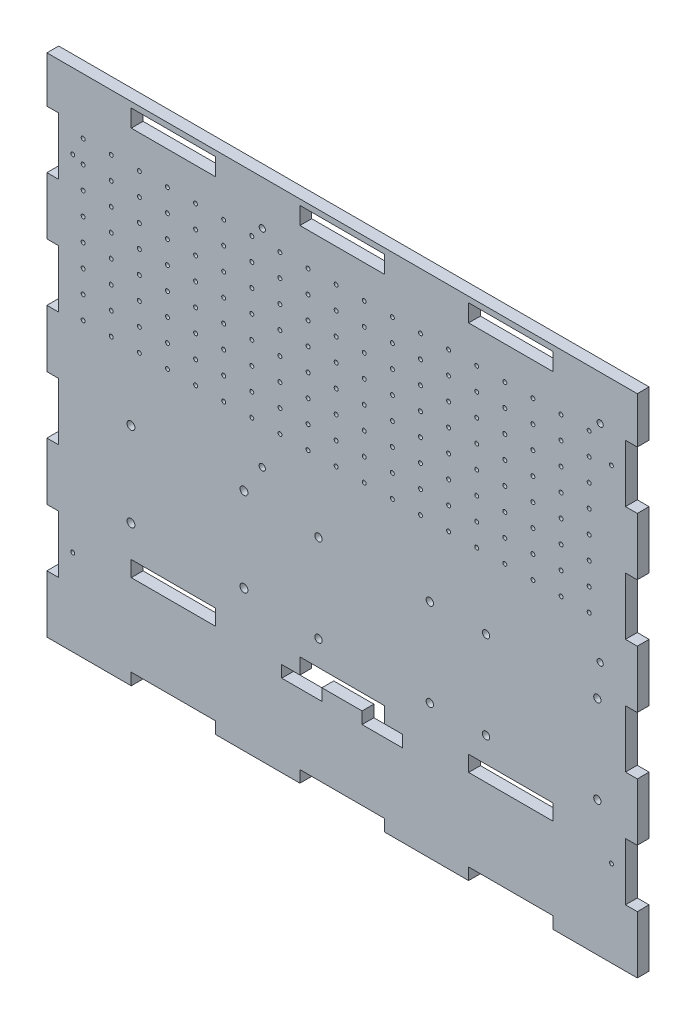
SolidWorks part; units mm, degrees
ref_plane "Front Plane" through (0, 0, 0) normal (0, 0, 1) x (1, 0, 0)
ref_plane "Top Plane" through (0, 0, 0) normal (0, 1, 0) x (1, 0, 0)
ref_plane "Right Plane" through (0, 0, 0) normal (1, 0, 0) x (0, 0, -1)
sketch "Sketch1" plane through (0, 0, 0) normal (0, 0, 1) x (1, 0, 0)
  line L1 (-127.8759, 139.2641) -> (138.8241, 139.2641)
  line L2 (-127.8759, 139.2641) -> (-127.8759, -84.2559)
  line L3 (-127.8759, -84.2559) -> (138.8241, -84.2559)
  line L4 (138.8241, 139.2641) -> (138.8241, -84.2559)
  dimension "D1" = 266.7
  dimension "D2" = 223.52
extrude "Boss-Extrude1" add sketch "Sketch1" along normal blind 5.334
sketch "Sketch2" plane through (0, 0, 5.334) normal (0, 0, 1) x (1, 0, 0)
  line L0 (-127.8759, -84.2559) -> (138.8241, -84.2559) construction
  line L1 (-89.7759, -84.2559) -> (-51.6759, -84.2559)
  line L2 (-89.7759, -84.2559) -> (-89.7759, -78.9219)
  line L3 (-89.7759, -78.9219) -> (-51.6759, -78.9219)
  line L4 (-51.6759, -84.2559) -> (-51.6759, -78.9219)
  line L5 (-89.7759, -78.9219) -> (-127.8759, -78.9219) construction
  line L6 (-13.5759, -84.2559) -> (24.5241, -84.2559)
  line L7 (-13.5759, -84.2559) -> (-13.5759, -78.9219)
  line L8 (-13.5759, -78.9219) -> (24.5241, -78.9219)
  line L9 (24.5241, -84.2559) -> (24.5241, -78.9219)
  line L10 (62.6241, -84.2559) -> (100.7241, -84.2559)
  line L11 (62.6241, -84.2559) -> (62.6241, -78.9219)
  line L12 (62.6241, -78.9219) -> (100.7241, -78.9219)
  line L13 (100.7241, -84.2559) -> (100.7241, -78.9219)
  line L14 (-127.8759, 139.2641) -> (-127.8759, -84.2559) construction
  line L15 (-51.6759, -78.9219) -> (-13.5759, -78.9219) construction
  line L16 (24.5241, -78.9219) -> (62.6241, -78.9219) construction
  line L17 (62.6241, -78.9219) -> (62.364, -79.7896) construction
  line L18 (100.7241, -78.9219) -> (138.8241, -78.9219) construction
  line L19 (138.8241, -84.2559) -> (138.8241, 139.2641) construction
  line L20 (-127.8759, 27.5041) -> (138.8241, 27.5041) construction
  line L21 (100.7241, 139.2641) -> (100.7241, 133.9301)
  line L22 (62.6241, 133.9301) -> (100.7241, 133.9301)
  line L23 (62.6241, 139.2641) -> (62.6241, 133.9301)
  line L24 (24.5241, 139.2641) -> (24.5241, 133.9301)
  line L25 (-13.5759, 133.9301) -> (24.5241, 133.9301)
  line L26 (-13.5759, 139.2641) -> (-13.5759, 133.9301)
  line L27 (-51.6759, 139.2641) -> (-51.6759, 133.9301)
  line L28 (-89.7759, 133.9301) -> (-51.6759, 133.9301)
  line L29 (-89.7759, 139.2641) -> (-89.7759, 133.9301)
  line L30 (62.6241, 139.2641) -> (100.7241, 139.2641)
  line L31 (-13.5759, 139.2641) -> (24.5241, 139.2641)
  line L32 (-89.7759, 139.2641) -> (-51.6759, 139.2641)
  dimension "D1" = 5.334
extrude "Cut-Extrude1" cut sketch "Sketch2" against normal through all
sketch "Sketch5" plane through (0, 0, 5.334) normal (0, 0, 1) x (1, 0, 0)
  line L0 (-51.6759, -34.8224) -> (-13.5759, -34.8224) construction
  line L1 (-89.7759, -34.8224) -> (-51.6759, -34.8224)
  line L2 (-89.7759, -34.8224) -> (-89.7759, -41.9344)
  line L3 (-89.7759, -41.9344) -> (-51.6759, -41.9344)
  line L4 (-51.6759, -34.8224) -> (-51.6759, -41.9344)
  line L5 (-13.5759, -34.8224) -> (24.5241, -34.8224)
  line L6 (-13.5759, -34.8224) -> (-13.5759, -41.9344)
  line L7 (-13.5759, -41.9344) -> (24.5241, -41.9344)
  line L8 (24.5241, -34.8224) -> (24.5241, -41.9344)
  line L9 (62.6241, -34.8224) -> (100.7241, -34.8224)
  line L10 (62.6241, -34.8224) -> (62.6241, -41.9344)
  line L11 (62.6241, -41.9344) -> (100.7241, -41.9344)
  line L12 (100.7241, -34.8224) -> (100.7241, -41.9344)
  line L13 (-51.6759, -41.9344) -> (-13.5759, -41.9344) construction
  line L14 (24.5241, -34.8224) -> (62.6241, -34.8224) construction
  line L15 (24.5241, -41.9344) -> (62.6241, -41.9344) construction
  line L16 (-89.7759, -34.8224) -> (-127.8759, -34.8224) construction
  line L17 (-127.8759, 139.2641) -> (-127.8759, -84.2559) construction
  line L18 (-89.7759, -41.9344) -> (-127.8759, -41.9344) construction
  line L19 (100.7241, -34.8224) -> (138.8241, -34.8224) construction
  line L20 (138.8241, -84.2559) -> (138.8241, 139.2641) construction
  line L21 (100.7241, -41.9344) -> (138.8241, -41.9344) construction
  dimension "D1" = 7.112
extrude "Cut-Extrude3" cut sketch "Sketch5" against normal through all
sketch "Sketch8" plane through (0, 0, 5.334) normal (0, 0, 1) x (1, 0, 0)
  line L0 (-13.5759, -41.9344) -> (24.5241, -41.9344) construction
  line L1 (-21.7977, -47.2684) -> (-3.6478, -47.2684)
  line L2 (-21.7977, -47.2684) -> (-21.7977, -41.9344)
  line L3 (-21.7977, -41.9344) -> (-3.6478, -41.9344)
  line L4 (-3.6478, -47.2684) -> (-3.6478, -41.9344)
  line L5 (-3.6478, -47.2684) -> (14.5022, -47.2684) construction
  line L6 (14.5022, -41.9344) -> (32.6521, -41.9344)
  line L7 (14.5022, -41.9344) -> (14.5022, -47.2684)
  line L8 (14.5022, -47.2684) -> (32.6521, -47.2684)
  line L9 (32.6521, -41.9344) -> (32.6521, -47.2684)
  line L10 (14.5022, -47.2684) -> (14.3218, -49.4005) construction
  line L11 (14.5022, -41.9344) -> (-3.6478, -41.9344) construction
  line L12 (62.6241, -34.8224) -> (62.6241, -41.9344) construction
  line L13 (-51.6759, -41.9344) -> (-51.6759, -34.8224) construction
  dimension "D1" = 5.334
  dimension "D2" = 29.972
  dimension "D3" = 29.8782
extrude "Cut-Extrude6" cut sketch "Sketch8" against normal through all
sketch "Sketch9" plane through (0, 0, 5.334) normal (0, 0, 1) x (1, 0, 0)
  line L0 (-111.5143, 118.9789) -> (-98.8143, 118.9789) construction
  line L1 (-111.5143, 108.8189) -> (-98.8143, 108.8189) construction
  line L2 (-111.5143, 98.6589) -> (-98.8143, 98.6589) construction
  line L3 (-111.5143, 88.4989) -> (-98.8143, 88.4989) construction
  line L4 (-111.5143, 78.3389) -> (-98.8143, 78.3389) construction
  line L5 (-111.5143, 68.1789) -> (-98.8143, 68.1789) construction
  line L6 (-111.5143, 58.0189) -> (-98.8143, 58.0189) construction
  line L7 (-111.5143, 47.8589) -> (-98.8143, 47.8589) construction
  line L8 (-111.5143, 118.9789) -> (-111.5143, 108.8189) construction
  circle A0 centre (-111.5143, 118.9789) radius 0.889
  circle A1 centre (-98.8143, 118.9789) radius 0.889
  circle A2 centre (-86.1143, 118.9789) radius 0.889
  circle A3 centre (-73.4143, 118.9789) radius 0.889
  circle A4 centre (-60.7143, 118.9789) radius 0.889
  circle A5 centre (-48.0143, 118.9789) radius 0.889
  circle A6 centre (-35.3143, 118.9789) radius 0.889
  circle A7 centre (-22.6143, 118.9789) radius 0.889
  circle A8 centre (-9.9143, 118.9789) radius 0.889
  circle A9 centre (2.7857, 118.9789) radius 0.889
  circle A10 centre (15.4857, 118.9789) radius 0.889
  circle A11 centre (28.1857, 118.9789) radius 0.889
  circle A12 centre (40.8857, 118.9789) radius 0.889
  circle A13 centre (53.5857, 118.9789) radius 0.889
  circle A14 centre (66.2857, 118.9789) radius 0.889
  circle A15 centre (78.9857, 118.9789) radius 0.889
  circle A16 centre (91.6857, 118.9789) radius 0.889
  circle A17 centre (104.3857, 118.9789) radius 0.889
  circle A18 centre (117.0857, 118.9789) radius 0.889
  circle A19 centre (-111.5143, 108.8189) radius 0.889
  circle A20 centre (-98.8143, 108.8189) radius 0.889
  circle A21 centre (-86.1143, 108.8189) radius 0.889
  circle A22 centre (-73.4143, 108.8189) radius 0.889
  circle A23 centre (-60.7143, 108.8189) radius 0.889
  circle A24 centre (-48.0143, 108.8189) radius 0.889
  circle A25 centre (-35.3143, 108.8189) radius 0.889
  circle A26 centre (-22.6143, 108.8189) radius 0.889
  circle A27 centre (-9.9143, 108.8189) radius 0.889
  circle A28 centre (2.7857, 108.8189) radius 0.889
  circle A29 centre (15.4857, 108.8189) radius 0.889
  circle A30 centre (28.1857, 108.8189) radius 0.889
  circle A31 centre (40.8857, 108.8189) radius 0.889
  circle A32 centre (53.5857, 108.8189) radius 0.889
  circle A33 centre (66.2857, 108.8189) radius 0.889
  circle A34 centre (78.9857, 108.8189) radius 0.889
  circle A35 centre (91.6857, 108.8189) radius 0.889
  circle A36 centre (104.3857, 108.8189) radius 0.889
  circle A37 centre (117.0857, 108.8189) radius 0.889
  circle A38 centre (-111.5143, 98.6589) radius 0.889
  circle A39 centre (-98.8143, 98.6589) radius 0.889
  circle A40 centre (-86.1143, 98.6589) radius 0.889
  circle A41 centre (-73.4143, 98.6589) radius 0.889
  circle A42 centre (-60.7143, 98.6589) radius 0.889
  circle A43 centre (-48.0143, 98.6589) radius 0.889
  circle A44 centre (-35.3143, 98.6589) radius 0.889
  circle A45 centre (-22.6143, 98.6589) radius 0.889
  circle A46 centre (-9.9143, 98.6589) radius 0.889
  circle A47 centre (2.7857, 98.6589) radius 0.889
  circle A48 centre (15.4857, 98.6589) radius 0.889
  circle A49 centre (28.1857, 98.6589) radius 0.889
  circle A50 centre (40.8857, 98.6589) radius 0.889
  circle A51 centre (53.5857, 98.6589) radius 0.889
  circle A52 centre (66.2857, 98.6589) radius 0.889
  circle A53 centre (78.9857, 98.6589) radius 0.889
  circle A54 centre (91.6857, 98.6589) radius 0.889
  circle A55 centre (104.3857, 98.6589) radius 0.889
  circle A56 centre (117.0857, 98.6589) radius 0.889
  circle A57 centre (-111.5143, 88.4989) radius 0.889
  circle A58 centre (-98.8143, 88.4989) radius 0.889
  circle A59 centre (-86.1143, 88.4989) radius 0.889
  circle A60 centre (-73.4143, 88.4989) radius 0.889
  circle A61 centre (-60.7143, 88.4989) radius 0.889
  circle A62 centre (-48.0143, 88.4989) radius 0.889
  circle A63 centre (-35.3143, 88.4989) radius 0.889
  circle A64 centre (-22.6143, 88.4989) radius 0.889
  circle A65 centre (-9.9143, 88.4989) radius 0.889
  circle A66 centre (2.7857, 88.4989) radius 0.889
  circle A67 centre (15.4857, 88.4989) radius 0.889
  circle A68 centre (28.1857, 88.4989) radius 0.889
  circle A69 centre (40.8857, 88.4989) radius 0.889
  circle A70 centre (53.5857, 88.4989) radius 0.889
  circle A71 centre (66.2857, 88.4989) radius 0.889
  circle A72 centre (78.9857, 88.4989) radius 0.889
  circle A73 centre (91.6857, 88.4989) radius 0.889
  circle A74 centre (104.3857, 88.4989) radius 0.889
  circle A75 centre (117.0857, 88.4989) radius 0.889
  circle A76 centre (-111.5143, 78.3389) radius 0.889
  circle A77 centre (-98.8143, 78.3389) radius 0.889
  circle A78 centre (-86.1143, 78.3389) radius 0.889
  circle A79 centre (-73.4143, 78.3389) radius 0.889
  circle A80 centre (-60.7143, 78.3389) radius 0.889
  circle A81 centre (-48.0143, 78.3389) radius 0.889
  circle A82 centre (-35.3143, 78.3389) radius 0.889
  circle A83 centre (-22.6143, 78.3389) radius 0.889
  circle A84 centre (-9.9143, 78.3389) radius 0.889
  circle A85 centre (2.7857, 78.3389) radius 0.889
  circle A86 centre (15.4857, 78.3389) radius 0.889
  circle A87 centre (28.1857, 78.3389) radius 0.889
  circle A88 centre (40.8857, 78.3389) radius 0.889
  circle A89 centre (53.5857, 78.3389) radius 0.889
  circle A90 centre (66.2857, 78.3389) radius 0.889
  circle A91 centre (78.9857, 78.3389) radius 0.889
  circle A92 centre (91.6857, 78.3389) radius 0.889
  circle A93 centre (104.3857, 78.3389) radius 0.889
  circle A94 centre (117.0857, 78.3389) radius 0.889
  circle A95 centre (-111.5143, 68.1789) radius 0.889
  circle A96 centre (-98.8143, 68.1789) radius 0.889
  circle A97 centre (-86.1143, 68.1789) radius 0.889
  circle A98 centre (-73.4143, 68.1789) radius 0.889
  circle A99 centre (-60.7143, 68.1789) radius 0.889
  circle A100 centre (-48.0143, 68.1789) radius 0.889
  circle A101 centre (-35.3143, 68.1789) radius 0.889
  circle A102 centre (-22.6143, 68.1789) radius 0.889
  circle A103 centre (-9.9143, 68.1789) radius 0.889
  circle A104 centre (2.7857, 68.1789) radius 0.889
  circle A105 centre (15.4857, 68.1789) radius 0.889
  circle A106 centre (28.1857, 68.1789) radius 0.889
  circle A107 centre (40.8857, 68.1789) radius 0.889
  circle A108 centre (53.5857, 68.1789) radius 0.889
  circle A109 centre (66.2857, 68.1789) radius 0.889
  circle A110 centre (78.9857, 68.1789) radius 0.889
  circle A111 centre (91.6857, 68.1789) radius 0.889
  circle A112 centre (104.3857, 68.1789) radius 0.889
  circle A113 centre (117.0857, 68.1789) radius 0.889
  circle A114 centre (-111.5143, 58.0189) radius 0.889
  circle A115 centre (-98.8143, 58.0189) radius 0.889
  circle A116 centre (-86.1143, 58.0189) radius 0.889
  circle A117 centre (-73.4143, 58.0189) radius 0.889
  circle A118 centre (-60.7143, 58.0189) radius 0.889
  circle A119 centre (-48.0143, 58.0189) radius 0.889
  circle A120 centre (-35.3143, 58.0189) radius 0.889
  circle A121 centre (-22.6143, 58.0189) radius 0.889
  circle A122 centre (-9.9143, 58.0189) radius 0.889
  circle A123 centre (2.7857, 58.0189) radius 0.889
  circle A124 centre (15.4857, 58.0189) radius 0.889
  circle A125 centre (28.1857, 58.0189) radius 0.889
  circle A126 centre (40.8857, 58.0189) radius 0.889
  circle A127 centre (53.5857, 58.0189) radius 0.889
  circle A128 centre (66.2857, 58.0189) radius 0.889
  circle A129 centre (78.9857, 58.0189) radius 0.889
  circle A130 centre (91.6857, 58.0189) radius 0.889
  circle A131 centre (104.3857, 58.0189) radius 0.889
  circle A132 centre (117.0857, 58.0189) radius 0.889
  circle A133 centre (-111.5143, 47.8589) radius 0.889
  circle A134 centre (-98.8143, 47.8589) radius 0.889
  circle A135 centre (-86.1143, 47.8589) radius 0.889
  circle A136 centre (-73.4143, 47.8589) radius 0.889
  circle A137 centre (-60.7143, 47.8589) radius 0.889
  circle A138 centre (-48.0143, 47.8589) radius 0.889
  circle A139 centre (-35.3143, 47.8589) radius 0.889
  circle A140 centre (-22.6143, 47.8589) radius 0.889
  circle A141 centre (-9.9143, 47.8589) radius 0.889
  circle A142 centre (2.7857, 47.8589) radius 0.889
  circle A143 centre (15.4857, 47.8589) radius 0.889
  circle A144 centre (28.1857, 47.8589) radius 0.889
  circle A145 centre (40.8857, 47.8589) radius 0.889
  circle A146 centre (53.5857, 47.8589) radius 0.889
  circle A147 centre (66.2857, 47.8589) radius 0.889
  circle A148 centre (78.9857, 47.8589) radius 0.889
  circle A149 centre (91.6857, 47.8589) radius 0.889
  circle A150 centre (104.3857, 47.8589) radius 0.889
  circle A151 centre (117.0857, 47.8589) radius 0.889
  dimension "D1" = 19
  dimension "D5" = 1.778
  dimension "D2" = 12.7
  dimension "D4" = 10.16
  dimension "D3" = 8
extrude "Cut-Extrude7" cut sketch "Sketch9" against normal through all
sketch "Sketch10" plane through (0, 139.2641, 0) normal (0, 1, 0) x (1, 0, 0)
  line L0 (-13.5759, -5.334) -> (-51.6759, -5.334) construction
  line L1 (-51.6759, 0) -> (-13.5759, 0)
  line L2 (-51.6759, 0) -> (-51.6759, -5.334)
  line L3 (-51.6759, -5.334) -> (-13.5759, -5.334)
  line L4 (-13.5759, 0) -> (-13.5759, -5.334)
extrude "Boss-Extrude2" add sketch "Sketch10" along normal blind 10.16
sketch "Sketch12" plane through (-51.6759, 0, 0) normal (-1, 0, 0) x (0, 0, 1)
  line L0 (0, 133.9301) -> (0, 149.4241) construction
  line L1 (5.334, 149.4241) -> (0, 149.4241)
  line L2 (5.334, 149.4241) -> (5.334, 141.8041)
  line L3 (5.334, 141.8041) -> (0, 141.8041)
  line L4 (0, 149.4241) -> (0, 141.8041)
  dimension "D1" = 7.62
extrude "Boss-Extrude3" add sketch "Sketch12" along normal blind 76.2 and the other way blind 190.5
sketch "Sketch13" plane through (0, 139.2641, 0) normal (0, 1, 0) x (1, 0, 0)
  line L1 (-127.8759, 0) -> (-89.7759, 0)
  line L2 (-127.8759, 0) -> (-127.8759, -5.334)
  line L3 (-127.8759, -5.334) -> (-89.7759, -5.334)
  line L4 (-89.7759, 0) -> (-89.7759, -5.334)
extrude "Boss-Extrude4" add sketch "Sketch13" along normal blind 2.54
sketch "Sketch14" plane through (0, 139.2641, 0) normal (0, 1, 0) x (1, 0, 0)
  line L1 (24.5241, 0) -> (62.6241, 0)
  line L2 (24.5241, 0) -> (24.5241, -5.334)
  line L3 (24.5241, -5.334) -> (62.6241, -5.334)
  line L4 (62.6241, 0) -> (62.6241, -5.334)
extrude "Boss-Extrude5" add sketch "Sketch14" along normal blind 2.54
sketch "Sketch15" plane through (0, 139.2641, 0) normal (0, 1, 0) x (1, 0, 0)
  line L1 (100.7241, 0) -> (138.8241, 0)
  line L2 (100.7241, 0) -> (100.7241, -5.334)
  line L3 (100.7241, -5.334) -> (138.8241, -5.334)
  line L4 (138.8241, 0) -> (138.8241, -5.334)
extrude "Boss-Extrude6" add sketch "Sketch15" along normal blind 2.54
sketch "Sketch16" plane through (0, 0, 5.334) normal (0, 0, 1) x (1, 0, 0)
  line L0 (-127.8759, 149.4241) -> (-127.8759, -84.2559) construction
  line L1 (-127.8759, -32.327) -> (-122.5419, -32.327)
  line L2 (-127.8759, -32.327) -> (-127.8759, -58.2914)
  line L3 (-127.8759, -58.2914) -> (-122.5419, -58.2914)
  line L4 (-122.5419, -32.327) -> (-122.5419, -58.2914)
  line L5 (-122.5419, -32.327) -> (-122.5419, -6.3625) construction
  line L6 (-127.8759, 19.6019) -> (-122.5419, 19.6019)
  line L7 (-122.5419, -58.2914) -> (-122.5419, -84.2559) construction
  line L8 (-127.8759, -84.2559) -> (-89.7759, -84.2559) construction
  line L9 (-127.8759, 19.6019) -> (-127.8759, -6.3625)
  line L10 (-127.8759, -6.3625) -> (-122.5419, -6.3625)
  line L11 (-122.5419, 19.6019) -> (-122.5419, -6.3625)
  line L12 (-122.5419, 19.6019) -> (-122.5419, 45.5664) construction
  line L13 (5.4741, -78.9219) -> (5.4741, 149.4241) construction
  line L14 (-127.8759, 71.5308) -> (-122.5419, 71.5308)
  line L15 (-127.8759, 71.5308) -> (-127.8759, 45.5664)
  line L16 (-127.8759, 45.5664) -> (-122.5419, 45.5664)
  line L17 (-122.5419, 71.5308) -> (-122.5419, 45.5664)
  line L18 (-122.5419, 71.5308) -> (-122.5419, 97.4953) construction
  line L19 (24.5241, -78.9219) -> (-13.5759, -78.9219) construction
  line L20 (-127.8759, 97.4953) -> (-122.5419, 97.4953)
  line L21 (-127.8759, 97.4953) -> (-127.8759, 123.4597)
  line L22 (-127.8759, 123.4597) -> (-122.5419, 123.4597)
  line L23 (-122.5419, 97.4953) -> (-122.5419, 123.4597)
  line L24 (-122.5419, 123.4597) -> (-122.5419, 149.4241) construction
  line L25 (-127.8759, 149.4241) -> (138.8241, 149.4241) construction
  line L26 (133.4901, 123.4597) -> (133.4901, 149.4241) construction
  line L27 (133.4901, 71.5308) -> (133.4901, 97.4953) construction
  line L28 (133.4901, 19.6019) -> (133.4901, 45.5664) construction
  line L29 (133.4901, -58.2914) -> (133.4901, -84.2559) construction
  line L30 (133.4901, -32.327) -> (133.4901, -6.3625) construction
  line L31 (133.4901, 97.4953) -> (133.4901, 123.4597)
  line L32 (138.8241, 123.4597) -> (133.4901, 123.4597)
  line L33 (138.8241, 97.4953) -> (138.8241, 123.4597)
  line L34 (138.8241, 97.4953) -> (133.4901, 97.4953)
  line L35 (133.4901, 71.5308) -> (133.4901, 45.5664)
  line L36 (138.8241, 45.5664) -> (133.4901, 45.5664)
  line L37 (138.8241, 71.5308) -> (138.8241, 45.5664)
  line L38 (138.8241, 71.5308) -> (133.4901, 71.5308)
  line L39 (133.4901, 19.6019) -> (133.4901, -6.3625)
  line L40 (138.8241, -6.3625) -> (133.4901, -6.3625)
  line L41 (138.8241, 19.6019) -> (138.8241, -6.3625)
  line L42 (138.8241, 19.6019) -> (133.4901, 19.6019)
  line L43 (133.4901, -32.327) -> (133.4901, -58.2914)
  line L44 (138.8241, -58.2914) -> (133.4901, -58.2914)
  line L45 (138.8241, -32.327) -> (138.8241, -58.2914)
  line L46 (138.8241, -32.327) -> (133.4901, -32.327)
  dimension "D1" = 5.334
extrude "Cut-Extrude9" cut sketch "Sketch16" against normal through all
sketch "Sketch17" plane through (0, 0, 5.334) normal (0, 0, 1) x (1, 0, 0)
  line L1 (133.4901, 71.5308) -> (133.4901, 45.5664) construction
  circle A0 centre (120.7901, 16.1089) radius 1.651
  circle A1 centre (117.0857, 47.8589) radius 0.889 construction
  circle A2 centre (70.4981, 16.1089) radius 1.651
  circle A3 centre (70.4981, -23.5151) radius 1.651
  circle A4 centre (120.7901, -23.5151) radius 1.651
  circle A5 centre (45.0981, 16.1089) radius 1.651
  circle A6 centre (-5.1939, 16.1089) radius 1.651
  circle A7 centre (-5.1939, -23.5151) radius 1.651
  circle A8 centre (45.0981, -23.5151) radius 1.651
  dimension "D1" = 31.75
  dimension "D2" = 12.7
  dimension "D3" = 2
  dimension "D4" = 2
  dimension "D5" = 2
  dimension "D6" = 2
  dimension "D7" = 2
extrude "Cut-Extrude10" cut sketch "Sketch17" against normal through all
sketch "Sketch18" plane through (0, 0, 5.334) normal (0, 0, 1) x (1, 0, 0)
  line L0 (133.4901, 123.4597) -> (133.4901, 97.4953) construction
  line L1 (133.4901, 110.4775) -> (-122.5419, 110.4775) construction
  line L2 (-122.5419, 97.4953) -> (-122.5419, 123.4597) construction
  line L3 (-122.5419, -45.3092) -> (133.4901, -45.3092) construction
  line L4 (-122.5419, -58.2914) -> (-122.5419, -32.327) construction
  line L5 (133.4901, -32.327) -> (133.4901, -58.2914) construction
  line L6 (138.8241, 32.5841) -> (-127.8759, 32.5841) construction
  line L7 (138.8241, 19.6019) -> (138.8241, 45.5664) construction
  line L8 (-127.8759, 45.5664) -> (-127.8759, 19.6019) construction
  line L9 (5.4741, 149.4241) -> (5.4741, -78.9219) construction
  line L10 (-127.8759, 149.4241) -> (138.8241, 149.4241) construction
  line L11 (24.5241, -78.9219) -> (-13.5759, -78.9219) construction
  circle A0 centre (127.1401, 110.4775) radius 0.889
  circle A1 centre (-116.1919, 110.4775) radius 0.889
  circle A2 centre (-116.1919, -45.3092) radius 0.889
  circle A3 centre (127.1401, -45.3092) radius 0.889
  dimension "D3" = 1.778
  dimension "D1" = 0
  dimension "D2" = 6.35
extrude "Cut-Extrude11" cut sketch "Sketch18" against normal through all
sketch "Sketch19" plane through (0, 0, 0) normal (0, 0, -1) x (-1, 0, 0)
  circle A0 centre (89.9029, 17.5059) radius 1.778 construction
  circle A1 centre (89.9029, -20.5941) radius 1.778 construction
  circle A2 centre (38.8489, -20.5941) radius 1.778 construction
  circle A3 centre (38.8489, 17.5059) radius 1.778 construction
  circle A4 centre (89.9029, 17.5059) radius 1.778
  circle A5 centre (89.9029, -20.5941) radius 1.778
  circle A6 centre (38.8489, -20.5941) radius 1.778
  circle A7 centre (38.8489, 17.5059) radius 1.778
extrude "Cut-Extrude12" cut sketch "Sketch19" against normal through all
sketch "Sketch20" plane through (0, 0, 5.334) normal (0, 0, 1) x (1, 0, 0)
  line L0 (138.8241, 123.4597) -> (138.8241, 149.4241) construction
  line L1 (-127.8759, 149.4241) -> (138.8241, 149.4241)
  line L2 (-127.8759, 149.4241) -> (-127.8759, 144.3441)
  line L3 (-127.8759, 144.3441) -> (138.8241, 144.3441)
  line L4 (138.8241, 149.4241) -> (138.8241, 144.3441)
  dimension "D1" = 5.08
extrude "Cut-Extrude13" cut sketch "Sketch20" against normal through all
sketch "Sketch21" plane through (0, 0, 0) normal (0, 0, -1) x (-1, 0, 0)
  circle A0 centre (-122.0601, 30.8409) radius 1.397 construction
  circle A1 centre (-122.0601, 124.3129) radius 1.397 construction
  circle A2 centre (30.5939, 30.8409) radius 1.397 construction
  circle A3 centre (30.5939, 124.3129) radius 1.397 construction
  circle A4 centre (-122.0601, 30.8409) radius 1.397
  circle A5 centre (-122.0601, 124.3129) radius 1.397
  circle A6 centre (30.5939, 30.8409) radius 1.397
  circle A7 centre (30.5939, 124.3129) radius 1.397
extrude "Cut-Extrude14" cut sketch "Sketch21" against normal through all
equation "\"MDF\"= .21in"
equation "\"Foamcore\"= .13in"
equation "\"Gmaterial\"= \"MDF\""
equation "\"D1@Boss-Extrude1\"=\"MDF\""
equation "\"D1@Sketch2\"=\"MDF\""
equation "\"D1@Sketch5\"=\"MDF\"+0.07"
equation "\"D1@Sketch8\"=\"MDF\""
equation "\"D1@Sketch16\"=\"MDF\""
